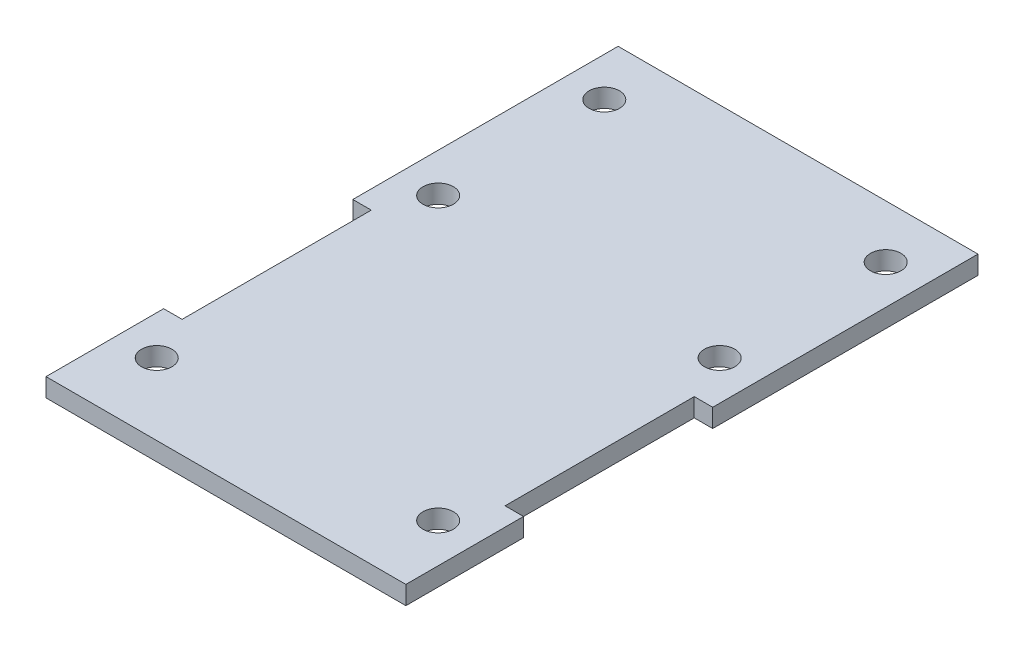
SolidWorks part; units mm, degrees
ref_plane "Front Plane" through (0, 0, 0) normal (0, 0, 1) x (1, 0, 0)
ref_plane "Top Plane" through (0, 0, 0) normal (0, 1, 0) x (1, 0, 0)
ref_plane "Right Plane" through (0, 0, 0) normal (1, 0, 0) x (0, 0, -1)
sketch "Sketch1" plane through (0, 0, 0) normal (0, 1, 0) x (1, 0, 0)
  line L1 (-18, 31) -> (18, 31)
  line L2 (-18, 31) -> (-18, -31)
  line L3 (-18, -31) -> (18, -31)
  line L4 (18, 31) -> (18, -31)
  line L5 (-18, 31) -> (18, -31) construction
  line L6 (-18, -31) -> (18, 31) construction
  point P0 (0, 0)
  dimension "D1" = 36
  dimension "D2" = 62
extrude "Base shape" add sketch "Sketch1" along normal blind 2
sketch "Sketch2" plane through (0, 2, 0) normal (0, 1, 0) x (1, 0, 0)
  line L0 (0, 31) -> (0, -31) construction
  line L1 (18, 31) -> (-18, 31) construction
  line L2 (-18, -31) -> (18, -31) construction
  line L4 (-18, 2.25) -> (-17.5, 2.25)
  line L5 (-18, 2.25) -> (-18, -18.25)
  line L6 (-18, -18.25) -> (-17.5, -18.25)
  line L7 (-17.5, 2.25) -> (-17.5, -18.25)
  line L8 (-17.5, -8) -> (-18, -8) construction
  line L9 (-15.25, -31) -> (-15.25, 31) construction
  line L11 (-18, -8) -> (18, -8) construction
  line L13 (15.25, 7.25) -> (15.25, -8) construction
  line L14 (15.25, 7.25) -> (0, 7.25) construction
  line L15 (18, -18.25) -> (17.5, -18.25)
  line L16 (17.5, 2.25) -> (17.5, -18.25)
  line L17 (18, 2.25) -> (17.5, 2.25)
  line L18 (18, 2.25) -> (18, -18.25)
  line L19 (18, -31) -> (18, 31) construction
  line L20 (-18, -31) -> (18, -31)
  line L21 (-18, -31) -> (-18, 15)
  line L22 (-18, 15) -> (18, 15)
  line L23 (18, -31) -> (18, 15)
  circle A0 centre (15.25, 7.25) radius 1.65
  circle A1 centre (15.25, -23.25) radius 1.65
  circle A2 centre (-15.25, 7.25) radius 1.65
  circle A3 centre (-15.25, -23.25) radius 1.65
  circle A4 centre (-15.25, 25.25) radius 1.65
  circle A5 centre (15.25, 25.25) radius 1.65
  line M13 (18, -31) -> (18, 31)
  line M15 (-18, 31) -> (-18, -31)
  dimension "D4" = 3.3
  dimension "D1" = 20.5
  dimension "D2" = 46
  dimension "D3" = 35
  dimension "D5" = 30.5
  dimension "D6" = 18
extrude "Cutouts" cut sketch "Sketch2" against normal up to next contours A2 | A0 | L17 L16 L15 M13 | L7 L4 L6 M15 | A3 | A1 | A4 | A5 region at (-17.75, 2, 8) region at (17.75, 2, 8) region at (15.25, 2, -7.25) region at (15.25, 2, 23.25) region at (-15.25, 2, -7.25) region at (-15.25, 2, 23.25)
sketch "Sketch3" plane through (0, 0, 0) normal (0, -1, 0) x (1, 0, 0)
  line L0 (18, -16.625) -> (19.5, -16.625) construction
  line L1 (19.5, 32.5) -> (-19.5, 32.5)
  line L2 (19.5, 32.5) -> (19.5, -32.5)
  line L3 (19.5, -32.5) -> (-19.5, -32.5)
  line L4 (-19.5, 32.5) -> (-19.5, -32.5)
  line L5 (19.5, 32.5) -> (-19.5, -32.5) construction
  line L6 (19.5, -32.5) -> (-19.5, 32.5) construction
  line L7 (0, -31) -> (0, -32.5) construction
  line L8 (-19.5, -31) -> (19.5, -31)
  line L9 (-19.5, -2.25) -> (19.5, -2.25)
  line L10 (-19.5, 18.25) -> (19.5, 18.25)
  line L11 (-19.5, 31) -> (19.5, 31)
  line L12 (-18, 18.25) -> (-17.5, 18.25)
  line L13 (-18, 31) -> (-18, 18.25)
  line L14 (18, 31) -> (-18, 31)
  line L15 (18, 18.25) -> (18, 31)
  line L16 (17.5, 18.25) -> (18, 18.25)
  line L17 (17.5, -2.25) -> (17.5, 18.25)
  line L18 (18, -2.25) -> (17.5, -2.25)
  line L19 (18, -31) -> (18, -2.25)
  line L20 (-18, -31) -> (18, -31)
  line L21 (-18, -2.25) -> (-18, -31)
  line L22 (-17.5, -2.25) -> (-18, -2.25)
  line L23 (-17.5, 18.25) -> (-17.5, -2.25)
  line L24 (-18, 18.25) -> (-17.5, 18.25)
  line L25 (-18, 31) -> (-18, 18.25)
  line L26 (18, 31) -> (-18, 31)
  line L27 (18, 18.25) -> (18, 31)
  line L28 (17.5, 18.25) -> (18, 18.25)
  line L29 (17.5, -2.25) -> (17.5, 18.25)
  line L30 (18, -2.25) -> (17.5, -2.25)
  line L31 (18, -31) -> (18, -2.25)
  line L32 (-18, -31) -> (18, -31)
  line L33 (-18, -2.25) -> (-18, -31)
  line L34 (-17.5, -2.25) -> (-18, -2.25)
  line L35 (-17.5, 18.25) -> (-17.5, -2.25)
  point P2 (0, 0)
  line M15 (18, -31) -> (18, -2.25)
  line M17 (-18, 31) -> (-18, 18.25)
  line M35 (-18, -2.25) -> (-18, -31)
  line M36 (18, 18.25) -> (18, 31)
  dimension "D2" = 1.5
  dimension "D1" = 0
extrude "Extra size" add sketch "Sketch3" against normal up to surface (2 mm away) contours L9 L4 L8 M35 | L9 L8 L2 M15 | L11 L4 L10 M17 | L11 L10 L2 M36 region at (18.75, 0, 24.625) region at (-18.75, 0, 24.625) region at (18.75, 0, -16.625) region at (-18.75, 0, -16.625) up to face at (15.25, 2, 24.9)
